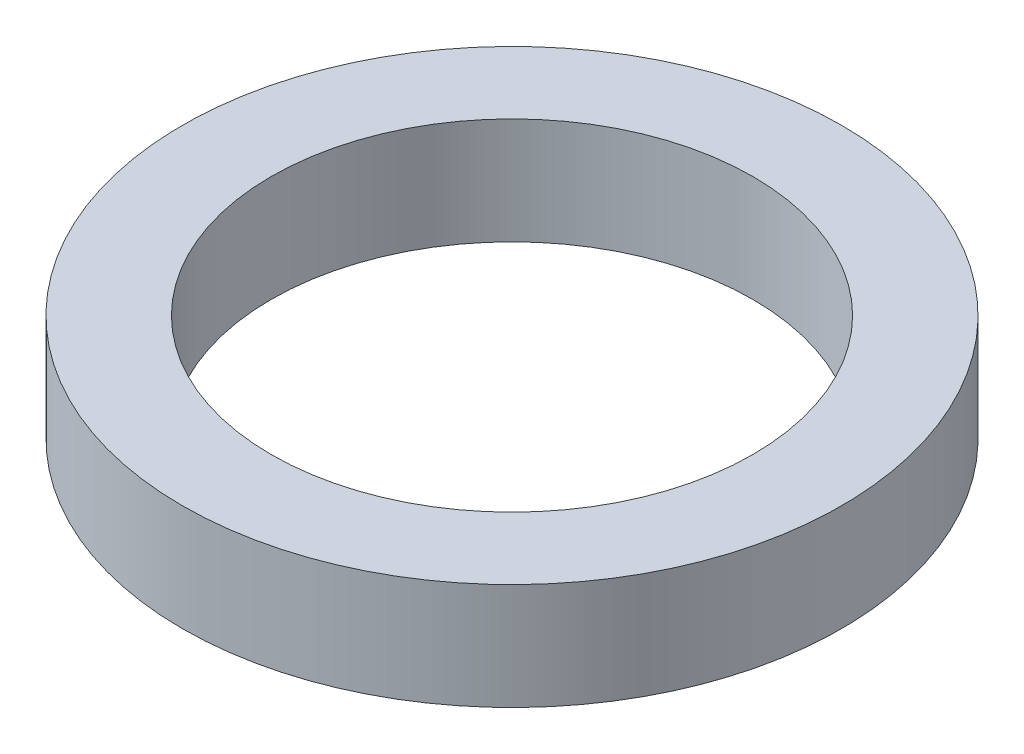
SolidWorks part; units mm, degrees
ref_plane "Front Plane" through (0, 0, 0) normal (0, 0, 1) x (1, 0, 0)
ref_plane "Top Plane" through (0, 0, 0) normal (0, 1, 0) x (1, 0, 0)
ref_plane "Right Plane" through (0, 0, 0) normal (1, 0, 0) x (0, 0, -1)
sketch "Sketch1" plane through (0, 0, 0) normal (0, 1, 0) x (1, 0, 0)
  circle A0 centre (0, 0) radius 65
  dimension "FLANGE_OD" = 130
extrude "Boss-Extrude1" add sketch "Sketch1" along normal blind 21
sketch "Sketch2" plane through (0, 0, 0) normal (0, 1, 0) x (1, 0, 0)
  circle A0 centre (0, 0) radius 47.5
  dimension "BORE_D" = 95
extrude "Cut-Extrude1" cut sketch "Sketch2" along normal through all
sketch "Sketch3" plane through (0, 21, 0) normal (0, 1, 0) x (1, 0, 0)
  circle A0 centre (0, 0) radius 26.418 construction
  circle A1 centre (-26.418, 0) radius 1.7084
  dimension "BOLT_D" = 3.4169
  dimension "BOLT_PCD" = 52.836
extrude "Cut-Extrude2" cut sketch "Sketch3" against normal blind 13.8549 rebuild error yes
pattern_circular "CirPattern1" count 5 over 360 rebuild error yes
